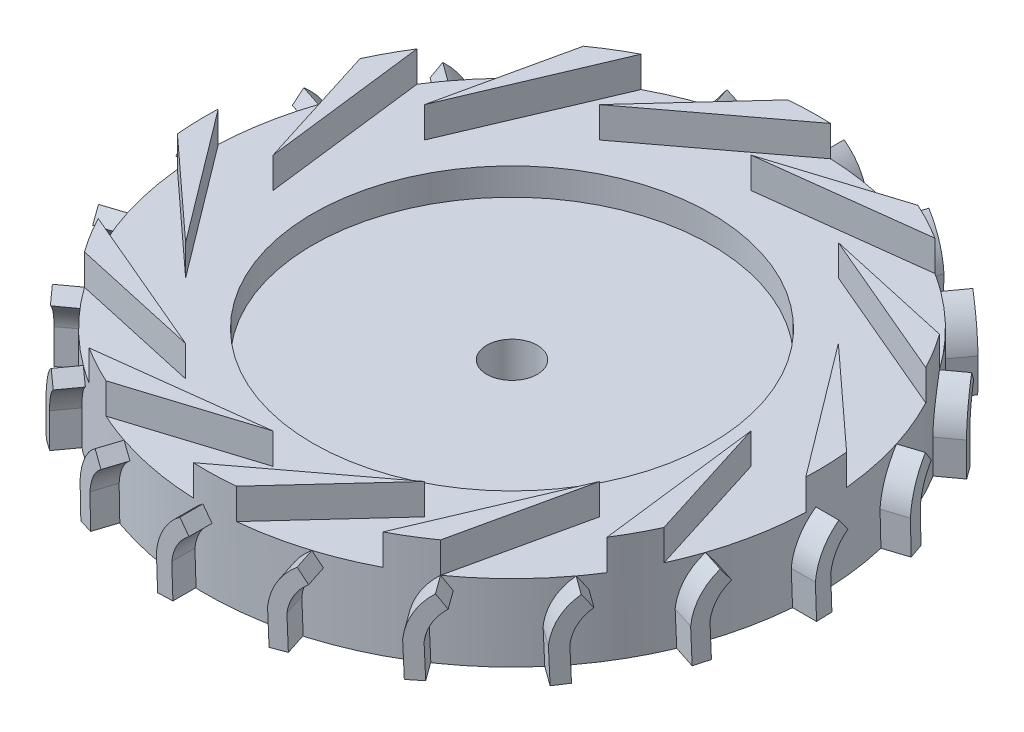
SolidWorks part; units mm, degrees
ref_plane "Front Plane" through (0, 0, 0) normal (0, 0, 1) x (1, 0, 0)
ref_plane "Top Plane" through (0, 0, 0) normal (0, 1, 0) x (1, 0, 0)
ref_plane "Right Plane" through (0, 0, 0) normal (1, 0, 0) x (0, 0, -1)
sketch "Sketch1" plane through (0, 0, 0) normal (1, 0, 0) x (0, 0, -1)
  line L0 (0, 26.2631) -> (0, -1.0485) construction
  line L1 (0, -1.0485) -> (-50.8, -1.0485)
  line L2 (-50.8, -1.0485) -> (-50.8, 11.6515)
  line L3 (-33.0001, 11.6515) -> (-50.8, 11.6515)
  line L4 (-33.0001, 11.6515) -> (-33.0001, 7.1515)
  line L5 (-33.0001, 7.1515) -> (0, 7.1515)
  line L6 (0, 7.1515) -> (0, -1.0485)
  dimension "D1" = 33.0001
  dimension "D2" = 50.8
  dimension "D3" = 4.5
  dimension "D4" = 12.7
revolve "Revolve1" add sketch "Sketch1" angle 360 about L0
sketch "Sketch2" plane through (0, 11.6515, 0) normal (0, 1, 0) x (1, 0, 0)
  line L8 (0, 39.6001) -> (19.9397, 39.6001) construction
  line L9 (0, 39.6001) -> (21.0453, 46.2356)
  line L10 (0, 39.6001) -> (27.1669, 42.9255)
  circle A0 centre (0, 0) radius 50.8 construction
  arc A1 (21.0453, 46.2356) -> (27.1669, 42.9255) centre (0, 0) cw
  circle A5 centre (0, 0) radius 33.0001 construction
  circle A7 centre (0, 0) radius 39.6001 construction
  point P9 (-2.4416, -40.4611)
  dimension "D1" = 66.0001
  dimension "D2" = 79.2001
  dimension "D3" = 17.5
extrude "Boss-Extrude1" add sketch "Sketch2" along normal blind 5.08
pattern_circular "CirPattern1" count 12 over 360 about axis through (0, 11.6515, 0) along (0, 1, 0) of "Boss-Extrude1"
ref_plane "Plane1" through (0, 0, 49.53) normal (0, 0, 1) x (1, 0, 0)
sketch "Sketch3" plane through (0, 0, 49.53) normal (0, 0, 1) x (1, 0, 0)
  line L0 (0, 0) -> (0, 9.7621) construction
  line L1 (0, -55) -> (0, 55) construction
  line L5 (-21.0453, 11.6515) -> (0, 11.6515) construction
  line L6 (-50.8, -1.0485) -> (50.8, -1.0485) construction
  line L7 (-4.3287, 4.6923) -> (-4.1287, -1.0485)
  line L10 (-1.7845, 4.6163) -> (-1.5903, -0.9601)
  line L11 (1.0729, 9.6084) -> (-0.4363, 11.6515)
  line L12 (-4.1287, -1.0485) -> (-1.5903, -0.9601)
  arc A4 (-0.4363, 11.6515) -> (-4.3287, 4.6923) centre (5.3144, 3.8668) ccw
  arc A5 (1.0729, 9.6084) -> (-1.7845, 4.6163) centre (5.3144, 3.8668) ccw
  dimension "D1" = 2.54
extrude "Boss-Extrude2" add sketch "Sketch3" along normal blind 5.08 and the other way blind 0.254
pattern_circular "CirPattern16" count 20 over 360 about axis through (0, -1.0485, 0) along (0, 1, 0) of "Boss-Extrude2"
sketch "Sketch4" plane through (0, 7.1515, 0) normal (0, 1, 0) x (1, 0, 0)
  circle A0 centre (0, 0) radius 4.191
  dimension "D1" = 8.382
extrude "Cut-Extrude1" cut sketch "Sketch4" against normal up to next
sketch "Sketch5" plane through (0, -1.0485, 0) normal (0, -1, 0) x (-1, 0, 0)
  circle A0 centre (0, 0) radius 38.1
  dimension "D1" = 76.2
extrude "Cut-Extrude2" cut sketch "Sketch5" against normal blind 7.62
sketch "Sketch6" plane through (0, 6.5715, 0) normal (0, -1, 0) x (1, 0, 0)
  circle A0 centre (0, 0) radius 19.05
  circle A1 centre (0, 0) radius 4.191 construction
  circle A2 centre (0, 0) radius 4.191
  dimension "D1" = 38.1
extrude "Boss-Extrude3" add sketch "Sketch6" along normal up to surface (7.62 mm away) up to face at (0, -1.0485, -38.1)
